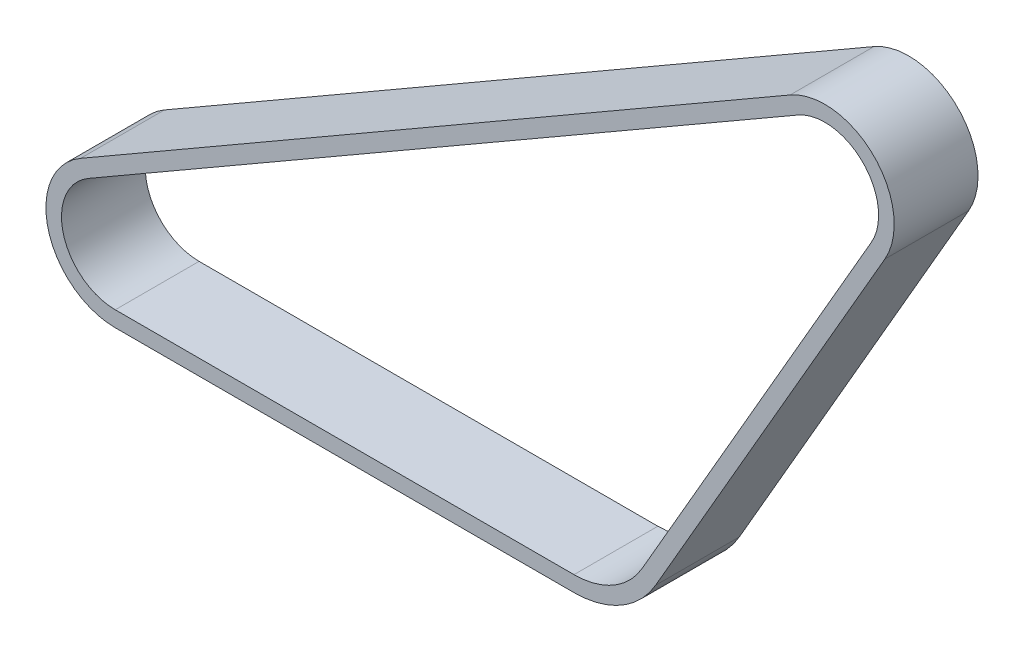
SolidWorks part; units mm, degrees
material "Silicon Rubber"
ref_plane "Front Plane" through (0, 0, 0) normal (0, 0, 1) x (1, 0, 0)
ref_plane "Top Plane" through (0, 0, 0) normal (0, 1, 0) x (1, 0, 0)
ref_plane "Right Plane" through (0, 0, 0) normal (1, 0, 0) x (0, 0, -1)
sketch "Sketch1" plane through (0, 0, 0) normal (0, 0, 1) x (1, 0, 0)
  line L2 (-93.472, -16) -> (0, -16)
  line L3 (-98.9489, 4.44) -> (45.6293, 87.9122)
  line L4 (60.5924, 72.9491) -> (13.8564, -8)
  line L5 (44.0418, 90.6619) -> (-100.5364, 7.1896)
  line L6 (-93.472, -19.175) -> (0, -19.175)
  line L7 (16.606, -9.5875) -> (63.342, 71.3616)
  arc A0 (0, -16) -> (13.8564, -8) centre (0, 0) ccw
  arc A1 (60.5924, 72.9491) -> (45.6293, 87.9122) centre (51.1062, 78.426) ccw
  arc A2 (-98.9489, 4.44) -> (-93.472, -16) centre (-93.472, -5.0463) ccw
  arc A3 (-100.5364, 7.1896) -> (-93.472, -19.175) centre (-93.472, -5.0463) ccw
  arc A4 (0, -19.175) -> (16.606, -9.5875) centre (0, 0) ccw
  arc A5 (63.342, 71.3616) -> (44.0418, 90.6619) centre (51.1062, 78.426) ccw
  dimension "D1" = 32
  dimension "D5" = 21.9075
  dimension "D6" = 172.8357
  dimension "D2" = 120
  dimension "D3" = 93.472
  dimension "D4" = 3.175
extrude "Boss-Extrude1" add sketch "Sketch1" along normal blind 17.0815
